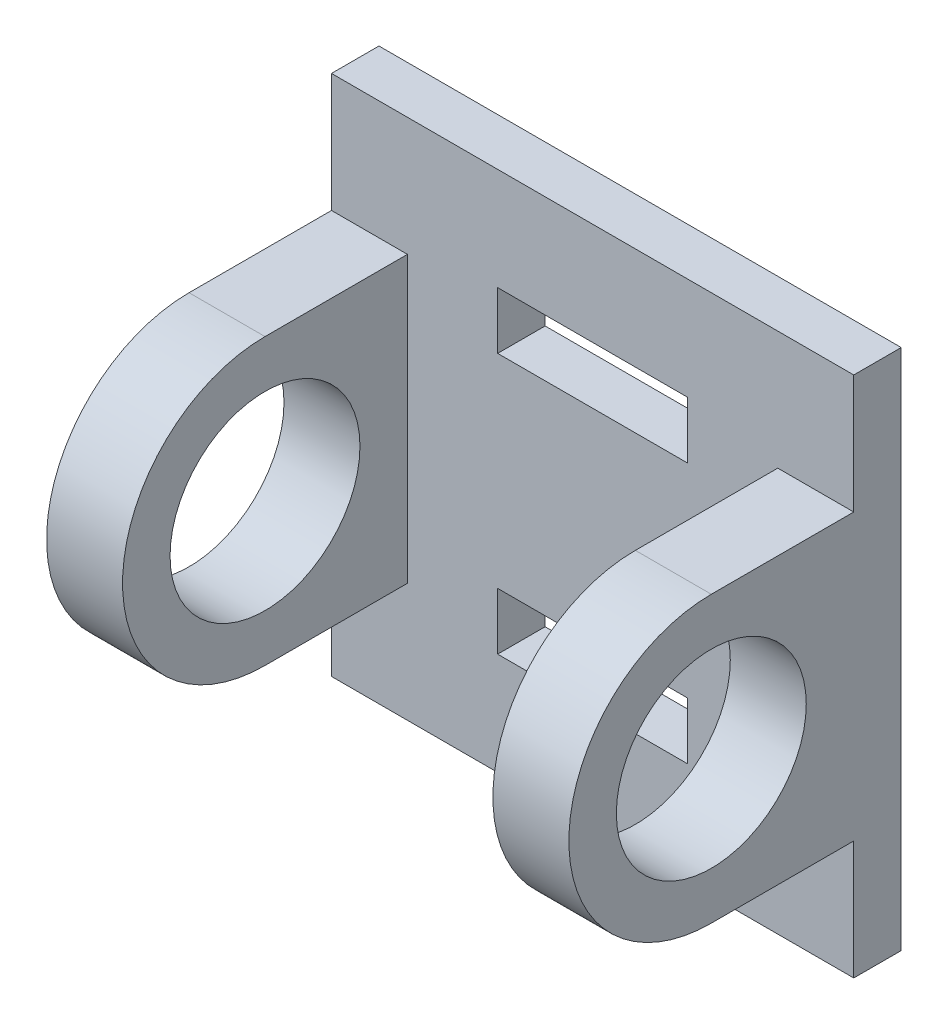
SolidWorks part; units mm, degrees
material "PLA"
ref_plane "Front Plane" through (0, 0, 0) normal (1, 0, 0) x (0, 1, 0)
ref_plane "Top Plane" through (0, 0, 0) normal (0, 0, 1) x (0, 1, 0)
ref_plane "Right Plane" through (0, 0, 0) normal (0, 1, 0) x (-1, 0, 0)
sketch "Sketch1" plane through (0, 0, 0) normal (0, 0, 1) x (0, 1, 0)
  line L1 (-13.75, -13.75) -> (13.75, -13.75)
  line L2 (-13.75, -13.75) -> (-13.75, 13.75)
  line L3 (-13.75, 13.75) -> (13.75, 13.75)
  line L4 (13.75, -13.75) -> (13.75, 13.75)
  line L5 (-13.75, -13.75) -> (13.75, 13.75) construction
  line L6 (-13.75, 13.75) -> (13.75, -13.75) construction
  point P0 (0, 0)
  dimension "D1" = 27.5
extrude "Boss-Extrude1" add sketch "Sketch1" along normal blind 2.5
sketch "Sketch2" plane through (13.75, 0, 0) normal (1, 0, 0) x (0, 1, 0)
  line L0 (-7.5, 2.5) -> (7.5, 2.5)
  line L1 (-13.75, 2.5) -> (13.75, 2.5) construction
  line L2 (7.5, 2.5) -> (7.5, 10)
  line L3 (-7.5, 2.5) -> (-7.5, 10)
  arc A0 (7.5, 10) -> (-7.5, 10) centre (0, 10) ccw
  circle A1 centre (0, 10) radius 5
  point P5 (0, 2.5)
  dimension "D1" = 10
  dimension "D2" = 2.5
  dimension "D3" = 7.5
extrude "Boss-Extrude2" add sketch "Sketch2" against normal blind 27.5
sketch "Sketch3" plane through (0, 0, 0) normal (1, 0, 0) x (0, 1, 0)
  line L1 (-13.75, 2.5) -> (13.75, 2.5)
  line L2 (-13.75, 2.5) -> (-13.75, 18.2629)
  line L3 (-13.75, 18.2629) -> (13.75, 18.2629)
  line L4 (13.75, 2.5) -> (13.75, 18.2629)
extrude "Cut-Extrude1" cut sketch "Sketch3" against normal offset from surface 4 and the other way offset from surface 4 up to face at (-13.75, 0, 4.6875) other way up to face at (13.75, 0, 4.6875)
sketch "Sketch4" plane through (0, 13.75, 0) normal (0, 1, 0) x (-1, 0, 0)
  line L1 (-13.75, 0) -> (13.75, 0)
  line L2 (-13.75, 0) -> (-13.75, 2.5)
  line L3 (-13.75, 2.5) -> (13.75, 2.5)
  line L4 (13.75, 0) -> (13.75, 2.5)
extrude "Cut-Extrude2" [suppressed] cut sketch "Sketch4" against normal up to surface (7.0945 mm away) up to face at (11.75, 7.5, 6.25)
sketch "Sketch5" plane through (0, -13.75, 0) normal (0, -1, 0) x (1, 0, 0)
  line L1 (-13.75, 0) -> (13.75, 0)
  line L2 (-13.75, 0) -> (-13.75, 2.5)
  line L3 (-13.75, 2.5) -> (13.75, 2.5)
  line L4 (13.75, 0) -> (13.75, 2.5)
extrude "Cut-Extrude3" [suppressed] cut sketch "Sketch5" against normal up to surface (5.4055 mm away) up to face at (-11.75, -7.5, 6.25)
sketch "Sketch6" plane through (0, 0, 2.5) normal (0, 0, 1) x (1, 0, 0)
  line L0 (0, 0) -> (0, 13.7151) construction
  line L2 (5, 5.3576) -> (-5, 5.3576)
  line L3 (5, 5.3576) -> (5, 8.3576)
  line L4 (5, 8.3576) -> (-5, 8.3576)
  line L5 (-5, 5.3576) -> (-5, 8.3576)
  line L6 (5, 5.3576) -> (-5, 8.3576) construction
  line L7 (5, 8.3576) -> (-5, 5.3576) construction
  point P2 (0, 6.8576)
  point P4 (0, 0)
  dimension "D1" = 10
  dimension "D2" = 3
extrude "Cut-Extrude4" cut sketch "Sketch6" against normal through all
mirror "Mirror1" about plane through (0, 0, 0) normal (0, 1, 0) of "Cut-Extrude4"
equation "\"ball_diameter\"= 0.75in"
equation "\"wall_thickness\" = 0.25cm"
equation "\"track_length\" = 25cm"
equation "\"axle\" = 5mm"
equation "\"pillar_width\" = 2.75cm"
equation "\"D1@Sketch1\"=\"pillar_width\""
equation "\"D1@Boss-Extrude1\"=\"wall_thickness\""
